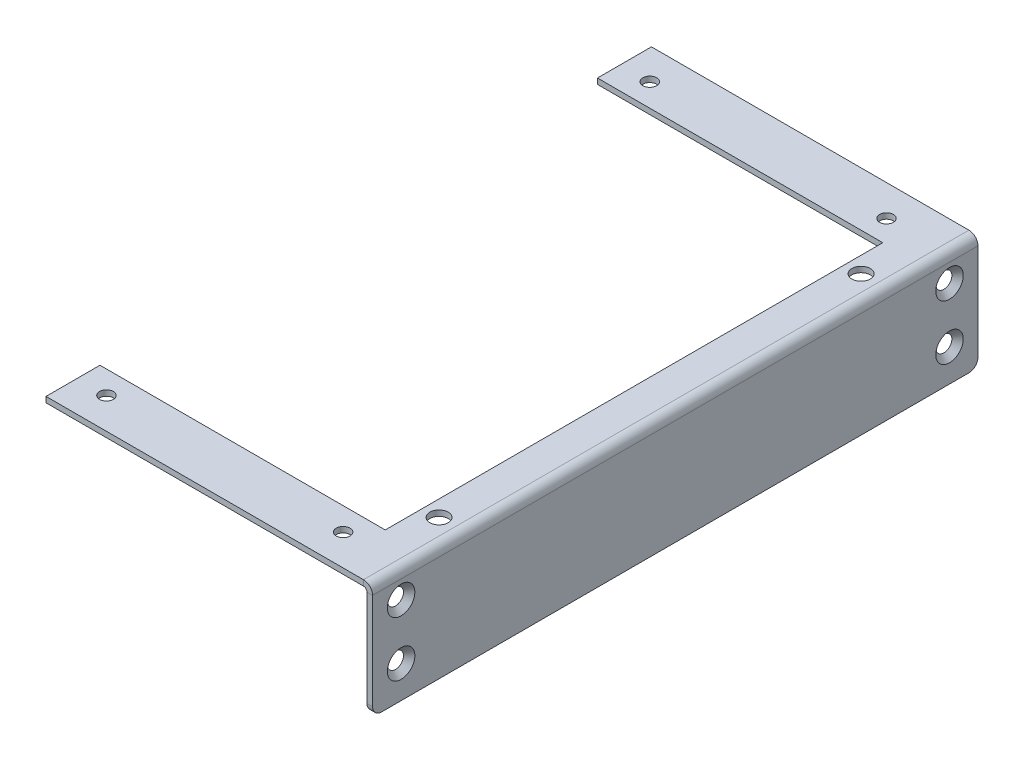
SolidWorks part; units mm, degrees
note: The reader was unsure of these and kept them because the rebuilt part matched: thickness of "Base-Flange1", "Edge-Flange1", "Sheet-Metal8", "Sheet-Metal9", "Sheet-Metal10", "Sheet-Metal12", "Sheet-Metal13", "Sheet-Metal14", "Sheet-Metal16"; flange length of "Edge-Flange1".
material "Plain Carbon Steel"
ref_plane "Front Plane" through (0, 0, 0) normal (0, 0, 1) x (1, 0, 0)
ref_plane "Top Plane" through (0, 0, 0) normal (0, 1, 0) x (1, 0, 0)
ref_plane "Right Plane" through (0, 0, 0) normal (1, 0, 0) x (0, 0, -1)
sketch "Sketch1" plane through (0, 0, 0) normal (0, 1, 0) x (1, 0, 0)
  line L1 (0, 0) -> (71.22, 0)
  line L2 (0, 0) -> (0, 132.04)
  line L3 (0, 132.04) -> (71.22, 132.04)
  line L4 (71.22, 0) -> (71.22, 132.04)
  dimension "D1" = 71.22
  dimension "D2" = 132.04
base flange "Base-Flange1" sketch "Sketch1" thickness 1.2192 reverse thickness direction no parameters "D1"=1.27
edge flange "Edge-Flange1" sketch "Sketch27" flange angle 90 flange length 24.9792 flange position material inside bend radius 0.76 thickness 1.2192 relief rectangular parameters "D6"=10
sketch "Sketch27" plane through (71.22, -1.2192, 0) normal (-1, 0, 0) x (0, 0, -1)
  line L2 (0, 0) -> (0, 23.76)
  line L3 (0, 23.76) -> (132.04, 23.76)
  line L4 (132.04, 23.76) -> (132.04, 0)
  line L5 (132.04, 0) -> (0, 0) construction
  line L6 (132.04, 0) -> (0, 0)
bend "EdgeBend1" bend radius 0.76 bend angle 90 parameters "D5"=1
sketch "Sketch28" plane through (0, 0, 0) normal (0, 1, 0) x (1, 0, 0)
  line L0 (0, 132.04) -> (0, 0) construction
  line L1 (0, 120.27) -> (62.22, 120.27)
  line L2 (0, 120.27) -> (0, 11.77)
  line L3 (0, 11.77) -> (62.22, 11.77)
  line L4 (62.22, 120.27) -> (62.22, 11.77)
  line L5 (69.2408, 132.04) -> (0, 132.04) construction
  line L6 (0, 0) -> (69.2408, 0) construction
  dimension "D1" = 62.22
  dimension "D2" = 11.77
  dimension "D3" = 11.77
extrude "Cut-Extrude2" cut sketch "Sketch28" against normal up to next normal cut yes
sketch "Sketch30" plane through (0, 0, 0) normal (0, 1, 0) x (1, 0, 0)
  line L0 (69.2408, 132.04) -> (0, 132.04) construction
  line L1 (0, 132.04) -> (0, 120.27) construction
  line L2 (0, 11.77) -> (0, 0) construction
  line L3 (0, 0) -> (69.2408, 0) construction
  point P0 (6.41, 125.27)
  point P1 (58.03, 125.27)
  point P2 (6.41, 6.77)
  point P3 (58.03, 6.77)
  dimension "D1" = 6.77
  dimension "D2" = 6.77
  dimension "D3" = 6.41
  dimension "D4" = 51.62
  dimension "D5" = 51.62
  dimension "D6" = 6.41
  dimension "D7" = 6.77
  dimension "D8" = 6.77
sketch "Sketch32" plane through (71.22, 0, 0) normal (1, 0, 0) x (0, 0, -1)
  line L0 (0, -24.9792) -> (0, -1.9792) construction
  line L1 (132.04, -24.9792) -> (0, -24.9792) construction
  line L2 (132.04, -1.9792) -> (132.04, -24.9792) construction
  point P0 (6.22, -5.9492)
  point P1 (125.82, -5.9492)
  point P2 (125.82, -17.9492)
  point P3 (6.22, -17.9492)
  dimension "D1" = 6.22
  dimension "D2" = 6.22
  dimension "D3" = 7.03
  dimension "D4" = 12
  dimension "D5" = 7.03
  dimension "D6" = 6.22
  dimension "D7" = 6.22
  dimension "D8" = 12
hole_wizard "CSK for M3 Cross Countersunk Head Screw4" positions "3DSketch6" profile "Sketch33" countersink size "M3" standard "AS" end condition through all
sketch3d "3DSketch6"
  point P0 (71.22, -5.9492, -6.22)
  point P3 (71.22, -17.9492, -6.22)
  point P6 (71.22, -5.9492, -125.82)
  point P9 (71.22, -17.9492, -125.82)
sketch "Sketch33" plane through (71.22, -5.9492, -6.22) normal (0, 1, 0) x (0, 0, -1)
  line L0 (0, 0) -> (0, 71.22)
  line L1 (0, 71.22) -> (1.7, 71.22)
  line L2 (1.7, 71.22) -> (1.7, 1.2554)
  line L3 (1.7, 1.2554) -> (3, 0)
  line L5 (3, 0) -> (0, 0)
  line L6 (-1.7, 1.2554) -> (-3, 0) construction
  line L11 (0, -6.35) -> (0, 107.95) construction
  dimension "Thru Hole Dia." = 3.4
  dimension "Thru Hole Depth" = 71.22
  dimension "Near C'Sink Dia." = 6
  dimension "Near C'Sink Angle" = 92
hole_wizard "Ø3.0mm Dowel Hole1" positions "3DSketch7" profile "Sketch34" hole size "Ø3.0" standard "AS" end condition up to next
sketch3d "3DSketch7"
  point P0 (6.41, 0, -125.27)
  point P3 (58.03, 0, -125.27)
  point P6 (58.03, 0, -6.77)
  point P9 (6.41, 0, -6.77)
sketch "Sketch34" plane through (6.41, 0, -125.27) normal (1, 0, 0) x (0, 0, 1)
  line L0 (0, 0) -> (0, 1.2192)
  line L1 (0, 1.2192) -> (1.5, 1.2192)
  line L2 (1.5, 1.2192) -> (1.5, 0)
  line L5 (1.5, 0) -> (0, 0)
  line L11 (0, -6.35) -> (0, 107.95) construction
  dimension "Thru Hole Dia." = 3
  dimension "Thru Hole Depth" = 1.2192
sketch "Sketch35" plane through (71.22, 0, 0) normal (1, 0, 0) x (0, 0, -1)
  line L1 (0, -24.9792) -> (1.98, -24.9792)
  line L2 (0, -24.9792) -> (0, -22.9992)
  line L5 (132.04, -24.9792) -> (130.06, -24.9792)
  line L6 (132.04, -24.9792) -> (132.04, -22.9992)
  arc A0 (0, -22.9992) -> (1.98, -24.9792) centre (1.98, -22.9992) ccw
  arc A1 (130.06, -24.9792) -> (132.04, -22.9992) centre (130.06, -22.9992) ccw
  dimension "D1" = 1.98
  dimension "D2" = 1.98
  dimension "D3" = 1.98
  dimension "D4" = 1.98
extrude "Cut-Extrude3" cut sketch "Sketch35" against normal up to next normal cut yes
sketch "Sketch36" plane through (0, 0, 0) normal (0, 1, 0) x (1, 0, 0)
  line L1 (62.22, 11.77) -> (62.22, 120.27) construction
  line L2 (69.2408, 132.04) -> (0, 132.04) construction
  line L3 (0, 0) -> (69.2408, 0) construction
  point P0 (65.72, 112.04)
  point P1 (65.72, 20)
  dimension "D1" = 3.5
  dimension "D2" = 3.5
  dimension "D3" = 20
  dimension "D4" = 20
hole_wizard "Ø4.0mm Dowel Hole1" positions "Sketch37" profile "Sketch38" hole size "Ø4.0" standard "AS" end condition up to next
sketch "Sketch37" plane through (0, 0, 0) normal (0, 1, 0) x (1, 0, 0)
  point P0 (65.72, 112.04)
  point P3 (65.72, 20)
sketch "Sketch38" plane through (65.72, 0, -112.04) normal (1, 0, 0) x (0, 0, 1)
  line L0 (0, 0) -> (0, 1.2192)
  line L1 (0, 1.2192) -> (2, 1.2192)
  line L2 (2, 1.2192) -> (2, 0)
  line L5 (2, 0) -> (0, 0)
  line L11 (0, -6.35) -> (0, 107.95) construction
  dimension "Thru Hole Dia." = 4
  dimension "Thru Hole Depth" = 1.2192
sketch "Bend-Lines3" [suppressed] plane through (0, 0, 0) normal (0, 1, 0) x (1, 0, 0)
sketch "Bounding-Box3" [suppressed] plane through (0, 0, 0) normal (0, 1, 0) x (1, 0, 0)
sheet metal parameters "Sheet-Metal8" thickness 1.2192 parameters "D1"=1.27
flat pattern "Flat-Pattern8" [suppressed]
sketch "Bend-Lines4" plane through (0, 0, 0) normal (0, 1, 0) x (1, 0, 0)
sketch3d "Bounding-Box4" [suppressed]
  line L0 (0, 0, 0) -> (0, 128.5, 0) construction
  line L1 (70, 0, 0) -> (70, 128.5, 0) construction
  line L2 (0, 0, 0) -> (70, 0, 0) construction
  line L3 (0, 128.5, 0) -> (70, 128.5, 0) construction
sheet metal parameters "Sheet-Metal9" thickness 1.2192 parameters "D1"=1.27
flat pattern "Flat-Pattern8"
sketch "Bend-Lines4" plane through (0, 0, 0) normal (0, 1, 0) x (1, 0, 0)
  line L0 (69.2801, 0) -> (69.2801, 128.5) construction
  line L1 (69.2801, 0) -> (69.2801, 128.5) construction
sketch3d "Bounding-Box4" [suppressed]
  line L0 (0, 0, 0) -> (0, 128.5, 0) construction
  line L1 (103.5602, 0, 0) -> (103.5602, 128.5, 0) construction
  line L2 (0, 0, 0) -> (103.5602, 0, 0) construction
  line L3 (0, 128.5, 0) -> (103.5602, 128.5, 0) construction
bend of the flat pattern "Flatten-<EdgeBend1>1"
sheet metal parameters "Sheet-Metal10" thickness 1.2192 parameters "D1"=1.27
flat pattern "Flat-Pattern8"
sketch "Bend-Lines4" plane through (0, 0, 0) normal (0, 1, 0) x (1, 0, 0)
  line L0 (69.2801, 0) -> (69.2801, 128.5) construction
  line L1 (69.2801, 0) -> (69.2801, 128.5) construction
sketch3d "Bounding-Box4" [suppressed]
  line L0 (0, 0, 0) -> (0, 128.5, 0) construction
  line L1 (103.5602, 0, 0) -> (103.5602, 128.5, 0) construction
  line L2 (0, 0, 0) -> (103.5602, 0, 0) construction
  line L3 (0, 128.5, 0) -> (103.5602, 128.5, 0) construction
bend of the flat pattern "Flatten-<EdgeBend1>1"
sheet metal parameters "Sheet-Metal12" thickness 1.2192 parameters "D1"=1.27
flat pattern "Flat-Pattern8" [suppressed]
sketch "Bend-Lines4" plane through (0, 0, 0) normal (0, 1, 0) x (1, 0, 0)
  line L0 (69.8565, 0) -> (69.8565, 128.5) construction
  line L1 (69.8565, 0) -> (69.8565, 128.5) construction
sketch3d "Bounding-Box4" [suppressed]
  line L0 (0, 0, 0) -> (0, 128.5, 0) construction
  line L1 (105.9322, 0, 0) -> (105.9322, 128.5, 0) construction
  line L2 (0, 0, 0) -> (105.9322, 0, 0) construction
  line L3 (0, 128.5, 0) -> (105.9322, 128.5, 0) construction
bend of the flat pattern "Flatten-<EdgeBend1>1"
sketch "Sketch32-1" [suppressed] plane through (68.953, 0, 0) normal (0, 1, 0) x (0, 0, -1)
  line L0 (0, -36.9792) -> (0, 68.953) construction
  line L1 (128.5, -36.9792) -> (0, -36.9792) construction
  line L2 (128.5, 68.953) -> (128.5, -36.9792) construction
  point P0 (5.76, -9.9492)
  point P1 (122.74, -9.9492)
  point P2 (122.74, -29.9492)
  point P3 (5.76, -29.9492)
  dimension "D1" = 5.76
  dimension "D2" = 5.76
  dimension "D3" = 7.03
  dimension "D4" = 20
  dimension "D5" = 7.03
  dimension "D6" = 5.76
  dimension "D7" = 5.76
  dimension "D8" = 20
sheet metal parameters "Sheet-Metal13" thickness 1.2192 parameters "D1"=1.27
flat pattern "Flat-Pattern8" [suppressed]
sketch "Bend-Lines4" plane through (0, 0, 0) normal (0, 1, 0) x (1, 0, 0)
  line L0 (70.3165, 0) -> (70.3165, 132.04) construction
  line L1 (70.3165, 0) -> (70.3165, 132.04) construction
sketch3d "Bounding-Box4" [suppressed]
  line L0 (0, 0, 0) -> (0, 132.04, 0) construction
  line L1 (106.3922, 0, 0) -> (106.3922, 132.04, 0) construction
  line L2 (0, 0, 0) -> (106.3922, 0, 0) construction
  line L3 (0, 132.04, 0) -> (106.3922, 132.04, 0) construction
bend of the flat pattern "Flatten-<EdgeBend1>1"
sketch "Sketch32-1" [suppressed] plane through (69.413, 0, 0) normal (0, 1, 0) x (0, 0, -1)
  line L0 (0, -36.9792) -> (0, 69.413) construction
  line L1 (132.04, -36.9792) -> (0, -36.9792) construction
  line L2 (132.04, 69.413) -> (132.04, -36.9792) construction
  point P0 (6.22, -9.9492)
  point P1 (125.82, -9.9492)
  point P2 (125.82, -29.9492)
  point P3 (6.22, -29.9492)
  dimension "D1" = 6.22
  dimension "D2" = 6.22
  dimension "D3" = 7.03
  dimension "D4" = 20
  dimension "D5" = 7.03
  dimension "D6" = 6.22
  dimension "D7" = 6.22
  dimension "D8" = 20
sheet metal parameters "Sheet-Metal14" thickness 1.2192 parameters "D1"=1.27
flat pattern "Flat-Pattern8" [suppressed]
sketch "Bend-Lines4" plane through (0, 0, 0) normal (0, 1, 0) x (1, 0, 0)
  line L0 (70.3165, 0) -> (70.3165, 132.04) construction
  line L1 (70.3165, 0) -> (70.3165, 132.04) construction
sketch3d "Bounding-Box4" [suppressed]
  line L0 (94.3922, 0, 0) -> (94.3922, 132.04, 0) construction
  line L1 (0, 0, 0) -> (0, 132.04, 0) construction
  line L2 (94.3922, 0, 0) -> (0, 0, 0) construction
  line L3 (94.3922, 132.04, 0) -> (0, 132.04, 0) construction
bend of the flat pattern "Flatten-<EdgeBend1>1"
sketch "Sketch32-1" [suppressed] plane through (69.413, 0, 0) normal (0, 1, 0) x (0, 0, -1)
  line L0 (0, -22.9992) -> (0, 69.413) construction
  line L1 (130.06, -24.9792) -> (1.98, -24.9792) construction
  line L2 (132.04, 69.413) -> (132.04, -22.9992) construction
  point P0 (6.22, -5.9492)
  point P1 (125.82, -5.9492)
  point P2 (125.82, -17.9492)
  point P3 (6.22, -17.9492)
  dimension "D1" = 6.22
  dimension "D2" = 6.22
  dimension "D3" = 7.03
  dimension "D4" = 12
  dimension "D5" = 7.03
  dimension "D6" = 6.22
  dimension "D7" = 6.22
  dimension "D8" = 12
sheet metal parameters "Sheet-Metal16" thickness 1.2192 parameters "D1"=1.27
flat pattern "Flat-Pattern8" [suppressed]
sketch "Bend-Lines4" plane through (0, 0, 0) normal (0, 1, 0) x (1, 0, 0)
  line L0 (70.3165, 0) -> (70.3165, 132.04) construction
  line L1 (70.3165, 0) -> (70.3165, 132.04) construction
sketch3d "Bounding-Box4" [suppressed]
  line L0 (94.3922, 0, 0) -> (94.3922, 132.04, 0) construction
  line L1 (0, 0, 0) -> (0, 132.04, 0) construction
  line L2 (94.3922, 0, 0) -> (0, 0, 0) construction
  line L3 (94.3922, 132.04, 0) -> (0, 132.04, 0) construction
bend of the flat pattern "Flatten-<EdgeBend1>1"
sketch "Sketch32-1" [suppressed] plane through (69.413, 0, 0) normal (0, 1, 0) x (0, 0, -1)
  line L0 (0, -22.9992) -> (0, 69.413) construction
  line L1 (130.06, -24.9792) -> (1.98, -24.9792) construction
  line L2 (132.04, 69.413) -> (132.04, -22.9992) construction
  point P0 (6.22, -5.9492)
  point P1 (125.82, -5.9492)
  point P2 (125.82, -17.9492)
  point P3 (6.22, -17.9492)
  dimension "D1" = 6.22
  dimension "D2" = 6.22
  dimension "D3" = 7.03
  dimension "D4" = 12
  dimension "D5" = 7.03
  dimension "D6" = 6.22
  dimension "D7" = 6.22
  dimension "D8" = 12
